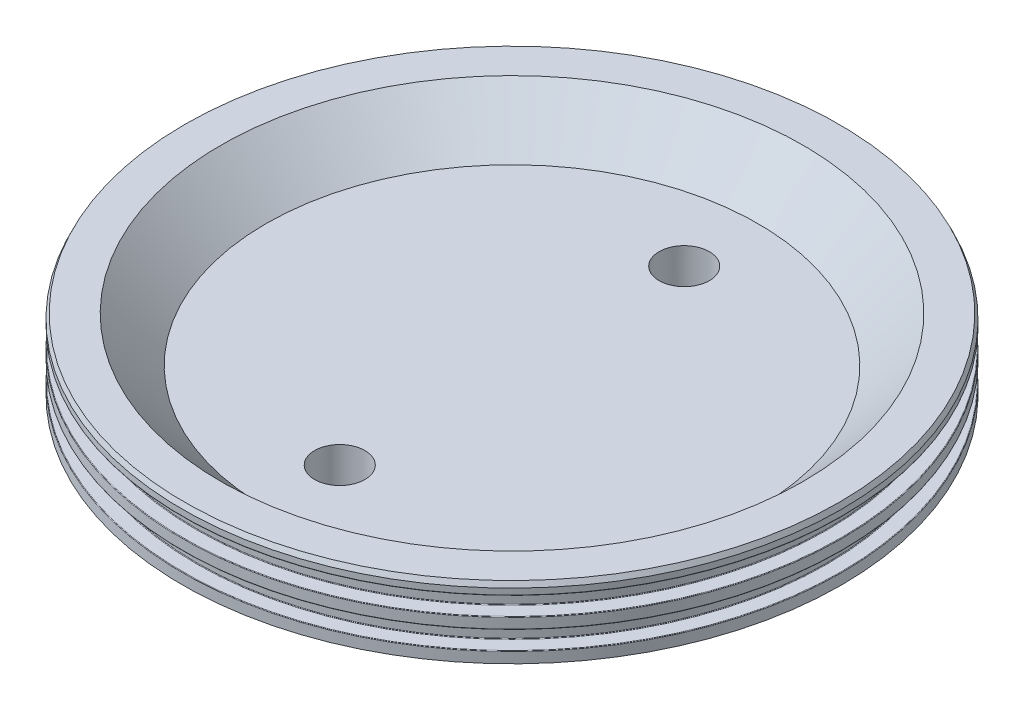
SolidWorks part; units mm, degrees
material "6061-T6 (SS)"
ref_plane "Front Plane" through (0, 0, 0) normal (0, 0, 1) x (1, 0, 0)
ref_plane "Top Plane" through (0, 0, 0) normal (0, 1, 0) x (1, 0, 0)
ref_plane "Right Plane" through (0, 0, 0) normal (1, 0, 0) x (0, 0, -1)
sketch "Sketch1" plane through (0, 0, 0) normal (0, 0, 1) x (1, 0, 0)
  line L0 (0, 48.1922) -> (0, -25.6743) construction
  line L1 (0, 0) -> (72.898, 0)
  line L2 (72.898, 0) -> (72.898, 2.4638)
  line L3 (72.898, 2.4638) -> (69.6468, 2.4638)
  line L4 (69.6468, 2.4638) -> (69.6468, 6.5278)
  line L5 (69.6468, 6.5278) -> (72.898, 6.5278)
  line L6 (72.898, 6.5278) -> (72.898, 8.9916)
  line L7 (72.898, 8.9916) -> (69.6468, 8.9916)
  line L8 (64.5668, 15.5956) -> (64.5668, 5.588)
  line L9 (64.5668, 5.588) -> (0, 5.588)
  line L10 (0, 5.588) -> (0, 0)
  line L11 (69.6468, 8.9916) -> (69.6468, 13.0556)
  line L12 (69.6468, 13.0556) -> (72.898, 13.0556)
  line L13 (72.898, 13.0556) -> (72.898, 15.5956)
  line L14 (72.898, 15.5956) -> (64.5668, 15.5956)
  dimension "D1" = 145.796
  dimension "D2" = 4.064
  dimension "D5" = 5.588
  dimension "D7" = 4.064
  dimension "D4" = 2.4638
  dimension "D8" = 2.54
  dimension "D3" = 69.6468
  dimension "D6" = 5.08
revolve "Revolve1" add sketch "Sketch1" angle 360 about L0
sketch "Sketch6" plane through (0, 0, 0) normal (0, -1, 0) x (1, 0, 0)
  circle A0 centre (0, 0) radius 66.04
  dimension "D1" = 132.08
extrude "Boss-Extrude1" add sketch "Sketch6" along normal blind 2.54
hole_wizard "Pipe Tap Drill for 1/4 Tap - GN2" positions "Sketch2" profile "Sketch3" hole size "1/4" standard "ANSI Inch" end condition through all
sketch "Sketch2" plane through (0, 5.588, 0) normal (0, 1, 0) x (1, 0, 0)
  point P4 (0, -38.1)
  dimension "D1" = 38.1
sketch "Sketch3" plane through (0, 5.588, 38.1) normal (1, 0, 0) x (0, 0, 1)
  line L0 (0, 0) -> (0, 8.128)
  line L1 (0, 8.128) -> (5.5626, 8.128)
  line L2 (5.5626, 8.128) -> (5.5626, 0)
  line L5 (5.5626, 0) -> (0, 0)
  line L11 (0, -6.35) -> (0, 107.95) construction
  dimension "Thru Hole Dia." = 11.1252
  dimension "Thru Hole Depth" = 8.128
fillet "CNC ID Fillet" radius 0.127 5 edges at (-69.6468, 6.5278, 0) (-69.6468, 2.4638, 0) (-69.6468, 13.0556, 0) (-69.6468, 8.9916, 0) (66.04, 0, 0)
fillet "CNC OD Fillet" radius 0.127 5 edges at (-72.898, 6.5278, 0) (-72.898, 2.4638, 0) (66.04, -2.54, 0) (-72.898, 13.0556, 0) (-72.898, 8.9916, 0)
chamfer "CNC Chamfers" distance 0.508 angle 65 1 edges at (-72.898, 15.5956, 0) first distance on face at (-64.5668, 15.5956, 0)
hole_wizard "Pipe Tap Drill for 1/4 Tap - Relief Valve" positions "Sketch13" profile "Sketch14" hole size "1/4" standard "ANSI Inch" end condition through all
sketch "Sketch13" plane through (0, -2.54, 0) normal (0, -1, 0) x (-1, 0, 0)
  point P4 (0, 38.1)
  dimension "D1" = 38.1
sketch "Sketch14" plane through (0, -2.54, -38.1) normal (1, 0, 0) x (0, 0, -1)
  line L0 (0, 0) -> (0, 18.1356)
  line L1 (0, 18.1356) -> (5.5626, 18.1356)
  line L2 (5.5626, 18.1356) -> (5.5626, 0)
  line L5 (5.5626, 0) -> (0, 0)
  line L11 (0, -6.35) -> (0, 107.95) construction
  dimension "Thru Hole Dia." = 11.1252
  dimension "Thru Hole Depth" = 18.1356
chamfer "Chamfer1" distance 10.16 angle 45 1 edges at (-64.5668, 5.588, 0)
equation "\"D3@Sketch1\"=5.484/2"
